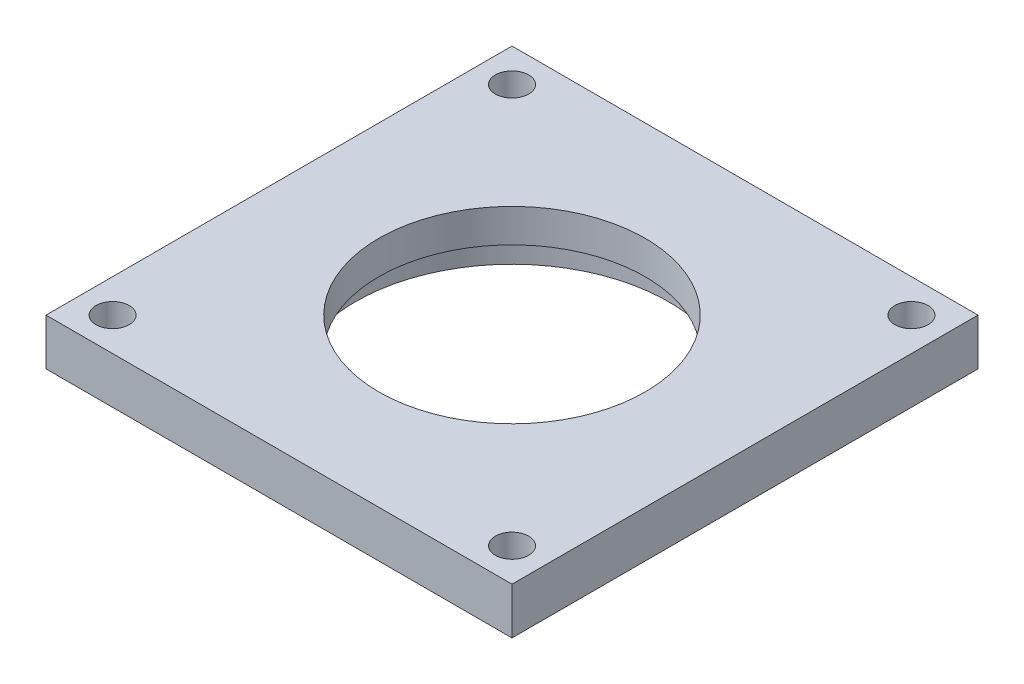
SolidWorks part; units mm, degrees
ref_plane "Płaszczyzna przednia" through (0, 0, 0) normal (0, 0, 1) x (1, 0, 0)
ref_plane "Płaszczyzna górna" through (0, 0, 0) normal (0, 1, 0) x (1, 0, 0)
ref_plane "Płaszczyzna prawa" through (0, 0, 0) normal (1, 0, 0) x (0, 0, -1)
sketch "Szkic1" plane through (0, 0, 0) normal (0, 1, 0) x (1, 0, 0)
  line L0 (0, 35) -> (70, 35) construction
  line L1 (0, 0) -> (70, 0)
  line L2 (0, 0) -> (0, 70)
  line L3 (0, 70) -> (70, 70)
  line L4 (70, 0) -> (70, 70)
  line L5 (35, 70) -> (35, 0) construction
  line L6 (5, 35) -> (5, 55)
  line L7 (15, 65) -> (55, 65)
  line L8 (65, 55) -> (65, 15)
  line L9 (55, 5) -> (15, 5)
  line L10 (5, 15) -> (5, 35)
  circle A0 centre (35, 35) radius 23.5
  arc A1 (15, 5) -> (5, 15) centre (15, 15) cw
  arc A2 (65, 15) -> (55, 5) centre (55, 15) cw
  arc A3 (55, 65) -> (65, 55) centre (55, 55) cw
  arc A4 (5, 55) -> (15, 65) centre (15, 55) cw
  circle A5 centre (35, 35) radius 20
  circle A6 centre (5, 5) radius 2.5
  circle A7 centre (65, 5) radius 2.5
  circle A8 centre (65, 65) radius 2.5
  circle A9 centre (5, 65) radius 2.5
  dimension "D3" = 60
  dimension "D5" = 47
  dimension "D6" = 10
  dimension "D7" = 60
  dimension "D1" = 70
  dimension "D2" = 70
  dimension "D4" = 60
  dimension "D8" = 60
extrude "Dodanie-wyciągnięcie1" add sketch "Szkic1" along normal blind 10 contours L1 L4 L3 L2 L6 A4 L7 A3 L8 A2 L9 A1 L10 | A4 L6 L10 A1 L9 A2 L8 A3 L7 A0 | A0 region at (0.9899, 0, -35) region at (5.8485, 0, -45) region at (12.1647, 0, -35)
extrude "Wytnij-wyciągnięcie1" cut sketch "Szkic1<3>" along normal blind 3 contours L1 L4 L3 L2 L6 A4 L7 A3 L8 A2 L9 A1 L10 region at (0.9899, 0, -35)
sketch "Szkic1<3>" plane through (0, 0, 0) normal (0, 1, 0) x (1, 0, 0) same geometry as "Szkic1"
extrude "Wytnij-wyciągnięcie2" cut sketch "Szkic1<4>" along normal blind 5 contours A0 A5 region at (12.1647, 0, -35)
sketch "Szkic1<4>" plane through (0, 0, 0) normal (0, 1, 0) x (1, 0, 0) same geometry as "Szkic1"
